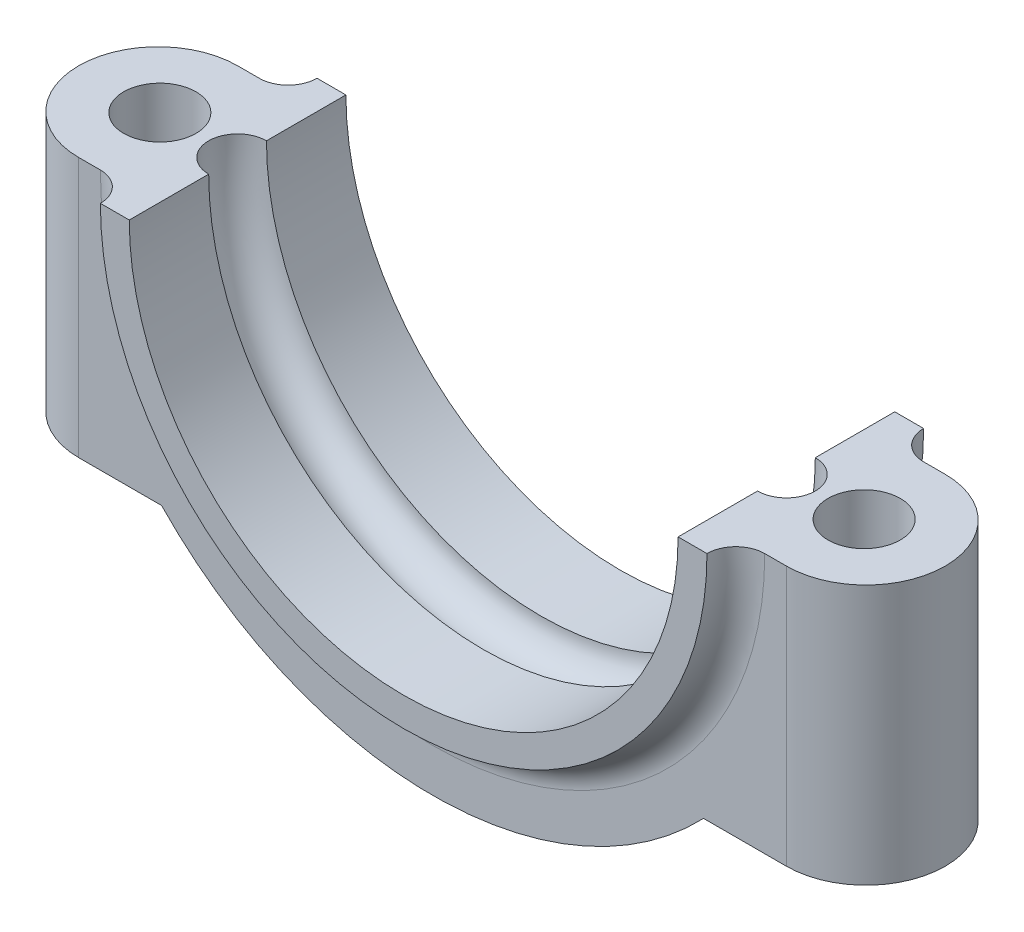
SolidWorks part; units mm, degrees
ref_plane "Front Plane" through (0, 0, 0) normal (0, 0, 1) x (1, 0, 0)
ref_plane "Top Plane" through (0, 0, 0) normal (0, 1, 0) x (1, 0, 0)
ref_plane "Right Plane" through (0, 0, 0) normal (1, 0, 0) x (0, 0, -1)
sketch "Sketch1" plane through (0, 0, 0) normal (0, 0, 1) x (1, 0, 0)
  line L0 (-30, 0) -> (30, 0) construction
  line L1 (0, 0) -> (0, -26) construction
  line L2 (19, 0) -> (30, 0)
  line L3 (30, 0) -> (30, -18)
  line L4 (30, -18) -> (18.7617, -18)
  line L5 (-19, 0) -> (-30, 0)
  line L6 (-30, 0) -> (-30, -18)
  line L7 (-30, -18) -> (-18.7617, -18)
  arc A1 (-19, 0) -> (19, 0) centre (0, 0) ccw
  arc A2 (-18.7617, -18) -> (18.7617, -18) centre (0, 0) ccw
  point P4 (0, 0)
  dimension "D2" = 60
  dimension "D3" = 19
  dimension "D4" = 26
  dimension "D1" = 18
extrude "Boss-Extrude1" add sketch "Sketch1" along normal mid plane 11
sketch "Sketch3" plane through (0, 0, 0) normal (0, 0, 1) x (1, 0, 0)
  line L6 (-21, 0) -> (-19, 0)
  line L7 (19, 0) -> (21, 0)
  arc A3 (-19, 0) -> (19, 0) centre (0, 0) ccw construction
  arc A4 (-21, 0) -> (21, 0) centre (0, 0) ccw
  arc A5 (-21, 0) -> (21, 0) centre (0, 0) ccw
  arc A6 (-19, 0) -> (19, 0) centre (0, 0) ccw
  dimension "D1" = 2
extrude "Boss-Extrude2" add sketch "Sketch3" along normal mid plane 15
sketch "Sketch4" plane through (0, 0, 0) normal (0, 1, 0) x (1, 0, 0)
  line L0 (-30, 0) -> (-18.7617, 0) construction
  line L1 (30, 0) -> (18.7617, 0) construction
  circle A0 centre (-24.3808, 0) radius 2.5
  circle A1 centre (24.3808, 0) radius 2.5
  dimension "D1" = 5
  dimension "D2" = 5
extrude "Cut-Extrude1" cut sketch "Sketch4" against normal through all
fillet "Fillet1" radius 2 2 edges at (0, -21, -5.5) (0, -21, 5.5)
sketch "Sketch5" plane through (0, 0, 0) normal (0, 1, 0) x (1, 0, 0)
  line L0 (19, -7.5) -> (19, 7.5) construction
  line L1 (0, 5.7163) -> (0, -5.7163) construction
  circle A0 centre (19, 0) radius 2
  point P8 (0, 0)
  dimension "D1" = 4
revolve "Cut-Revolve1" cut sketch "Sketch5" angle 360 about L1
fillet "Fillet2" 2 edges at (30, -9, 5.5) (30, -9, -5.5) type full round first side face at (0, -12.875, 5.5) second side face at (0, -12.875, -5.5) middle face at (30, -9, 0)
fillet "Fillet3" 2 edges at (-30, -9, -5.5) (-30, -9, 5.5) type full round first side face at (-1.375, -12.875, -5.5) second side face at (-1.375, -12.875, 5.5) middle face at (-30, -9, 0)
